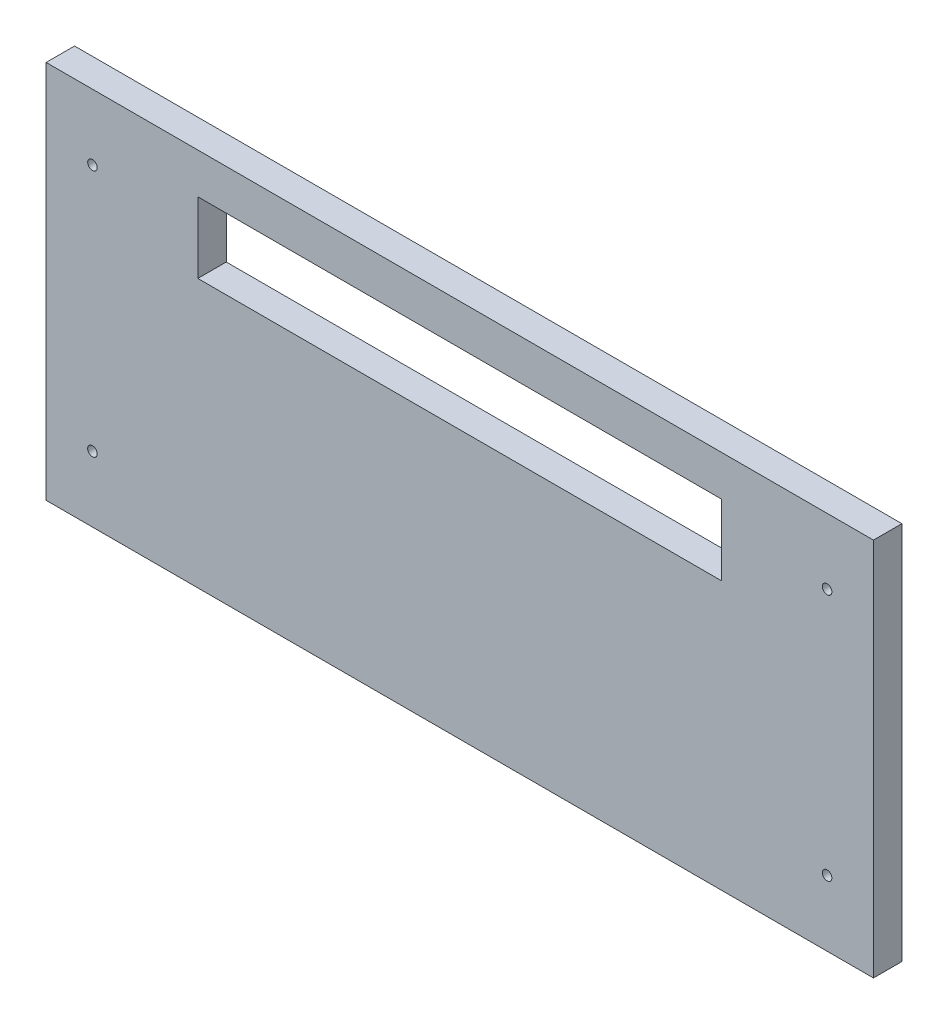
SolidWorks part; units mm, degrees
ref_plane "Front Plane" through (0, 0, 0) normal (0, 0, 1) x (1, 0, 0)
ref_plane "Top Plane" through (0, 0, 0) normal (0, 1, 0) x (1, 0, 0)
ref_plane "Right Plane" through (0, 0, 0) normal (1, 0, 0) x (0, 0, -1)
sketch "Sketch1" plane through (0, 0, 0) normal (0, 0, 1) x (1, 0, 0)
  line L1 (0, 0) -> (277.05, 0)
  line L2 (0, 0) -> (0, 127)
  line L3 (0, 127) -> (277.05, 127)
  line L4 (277.05, 0) -> (277.05, 127)
  line L5 (9.525, 127) -> (9.525, 0) construction
  line L7 (267.525, 127) -> (267.525, 0) construction
  circle A3 centre (15.525, 105) radius 1.6
  circle A4 centre (15.525, 22) radius 1.6
  circle A5 centre (261.525, 105) radius 1.6
  circle A6 centre (261.525, 22) radius 1.6
  dimension "D14" = 3.2
  dimension "D17" = 3.2
  dimension "D19" = 3.2
  dimension "D20" = 3.2
  dimension "D1" = 127
  dimension "D2" = 277.05
  dimension "D3" = 9.525
  dimension "D5" = 9.525
  dimension "D13" = 6
  dimension "D15" = 22
  dimension "D16" = 6
  dimension "D18" = 22
  dimension "D21" = 6
  dimension "D22" = 6
  dimension "D23" = 22
  dimension "D24" = 22
extrude "Wall" add sketch "Sketch1" along normal blind 9.525
sketch "Sketch2" plane through (0, 0, 9.525) normal (0, 0, 1) x (1, 0, 0)
  line L0 (277.05, 127) -> (0, 127) construction
  line L1 (0, 127) -> (0, 0) construction
  line L2 (95.53, 107.95) -> (138.525, 107.95) construction
  line L3 (181.52, 107.95) -> (138.525, 107.95) construction
  circle A0 centre (138.525, 107.95) radius 3.97
  circle A1 centre (95.53, 107.95) radius 3.97
  circle A2 centre (181.52, 107.95) radius 3.97
  point P4 (138.525, 127)
  dimension "D1" = 7.94
  dimension "D2" = 19.05
  dimension "D3" = 95.53
extrude "RodCutouts" [suppressed] cut sketch "Sketch2" against normal up to next
sketch "Sketch3" plane through (0, 0, 9.525) normal (0, 0, 1) x (1, 0, 0)
  line L0 (277.05, 127) -> (0, 127) construction
  line L1 (50.8, 89.7557) -> (226.25, 89.7557)
  line L2 (50.8, 89.7557) -> (50.8, 113.4443)
  line L3 (50.8, 113.4443) -> (226.25, 113.4443)
  line L4 (226.25, 89.7557) -> (226.25, 113.4443)
  line L5 (50.8, 89.7557) -> (226.25, 113.4443) construction
  line L6 (50.8, 113.4443) -> (226.25, 89.7557) construction
  line L7 (0, 127) -> (0, 0) construction
  point P0 (138.525, 101.6)
  point P9 (138.525, 127)
  dimension "D1" = 25.4
  dimension "D2" = 50.8
extrude "CannulusLargeCutout" cut sketch "Sketch3" against normal up to next
sketch "Sketch4" [suppressed] plane through (0, 0, 9.525) normal (0, 0, 1) x (1, 0, 0)
  line L0 (15.525, 103.5) -> (261.525, 103.5) construction
  line L1 (15.525, 105) -> (15.525, 22) construction
  line L2 (261.525, 105) -> (261.525, 22) construction
  circle A0 centre (38.525, 103.5) radius 7.5
  circle A1 centre (38.525, 63.5) radius 7.5
  circle A2 centre (88.525, 63.5) radius 7.5
  circle A3 centre (138.525, 63.5) radius 7.5
  circle A4 centre (88.525, 103.5) radius 7.5
  circle A5 centre (138.525, 103.5) radius 7.5
  circle A6 centre (188.525, 103.5) radius 7.5
  circle A7 centre (238.525, 103.5) radius 7.5
  circle A8 centre (188.525, 63.5) radius 7.5
  circle A9 centre (238.525, 63.5) radius 7.5
  circle A10 centre (38.525, 23.5) radius 7.5
  circle A11 centre (88.525, 23.5) radius 7.5
  circle A12 centre (138.525, 23.5) radius 7.5
  circle A13 centre (188.525, 23.5) radius 7.5
  circle A14 centre (238.525, 23.5) radius 7.5
  point P9 (15.525, 63.5)
  point P23 (138.525, 103.5)
  dimension "D1" = 15
  dimension "D2" = 5
  dimension "D4" = 3
extrude "CannulusHoles" [suppressed] cut sketch "Sketch4" against normal up to next
equation "\"Length\"= 283mm"
equation "\"Width\"= 225mm"
equation "\"WallThickness\"= 12.5mm"
equation "\"UpperWaterJacketThickness\"= 28mm"
equation "\"SpacerHeight\"= 80.2mm"
equation "\"SpacerCornerWidth\"= 10mm"
equation "\"SpacerCornerHeight\"= 60.16mm"
equation "\"SpacerPegDiameter\"= 10mm"
equation "\"SpacerPegHeight\"= 10mm"
equation "\"TubingShort\"= 110mm"
equation "\"TubingLong\"= 175mm"
equation "\"PlateLength\"= 252mm"
equation "\"PlateWidth\"= 190mm"
equation "\"PlateHoleDiameter\"= 5.9mm"
equation "\"PlateHoleBottom\"= 2mm"
equation "\"PlateHoleSide\"= 1.55mm"
equation "\"PlateHoleSpacing\"= 3.1mm"
equation "\"PlateThickness\"= 1.55mm"
equation "\"ReservoirBottom\"= 12.5mm"
equation "\"ReservoirSupportWidth\"= 12mm"
equation "\"ReservoirSupportHeight\"= 15.1mm"
equation "\"ReservoirSupportPlacementHeight\"= 50mm"
equation "\"ReservoirHoleDiameter\"= 12.7mm"
equation "\"ReservoirHoleRight\"= 25mm"
equation "\"ReservoirHoleTop\"= \"ReservoirSupportPlacementHeight\""
equation "\"ReservoirHeight\"= 90mm"
equation "\"ReservoirPortBottom\"= 4mm"
equation "\"ReservoirPortTop\"= 10mm"
equation "\"ReservoirPortWidth\"= 101mm"
equation "\"CustomSpacerWallThickness\"= 0.375in"
equation "\"CustomSpacerHeight\"= 5in"
equation "\"CustomSpacerRodHoleHeight\"= .75in"
equation "\"CustomSpacerRodHoleDiameter\"= .3125in"
equation "\"ScrewBlockSide\"= 12mm"
equation "\"ScrewBlockUpperHeight\"= 16mm"
equation "\"ScrewBlockLowerHeight\"= 16mm"
equation "\"InternalLength\"= \"Length\" - ( 2 * \"WallThickness\" )"
equation "\"InternalWidth\"= \"Width\" - ( 2 * \"WallThickness\" )"
equation "\"CustomSpacerPegHeight\"= 1in"
equation "\"CustomSpacerScrewBore\"=3.2mm"
equation "\"CustomSpacerScrewDepth\"=10mm"
equation "\"D1@Sketch1\"=\"CustomSpacerHeight\""
equation "\"D2@Sketch1\"=\"InternalLength\"+\"CustomSpacerWallThickness\"*2"
equation "\"D3@Sketch1\"=\"CustomSpacerWallThickness\""
equation "\"D5@Sketch1\"=\"CustomSpacerWallThickness\""
equation "\"D1@Wall\" = \"CustomSpacerWallThickness\""
equation "\"D13@Sketch1\"=\"ScrewBlockSide\"/2"
equation "\"D14@Sketch1\"=\"CustomSpacerScrewBore\""
equation "\"D15@Sketch1\"=\"ScrewBlockUpperHeight\"+\"ScrewBlockSide\"/2"
equation "\"D16@Sketch1\"=\"ScrewBlockSide\"/2"
equation "\"D17@Sketch1\"=\"CustomSpacerScrewBore\""
equation "\"D18@Sketch1\"=\"ScrewBlockLowerHeight\"+\"ScrewBlockSide\"/2"
equation "\"D19@Sketch1\"=\"CustomSpacerScrewBore\""
equation "\"D20@Sketch1\"=\"CustomSpacerScrewBore\""
equation "\"D21@Sketch1\"=\"ScrewBlockSide\"/2"
equation "\"D22@Sketch1\"=\"ScrewBlockSide\"/2"
equation "\"D23@Sketch1\"=\"ScrewBlockLowerHeight\"+\"ScrewBlockSide\"/2"
equation "\"D24@Sketch1\"=\"ScrewBlockUpperHeight\"+\"ScrewBlockSide\"/2"
equation "\"RodCutout\"=7.94"
equation "\"D1@Sketch2\"=\"RodCutout\""
equation "\"D3@Sketch2\"=86mm+9.53mm"
equation "\"CannulusTubingDiameter\"=15"
equation "\"D1@Sketch4\"=\"CannulusTubingDiameter\""
